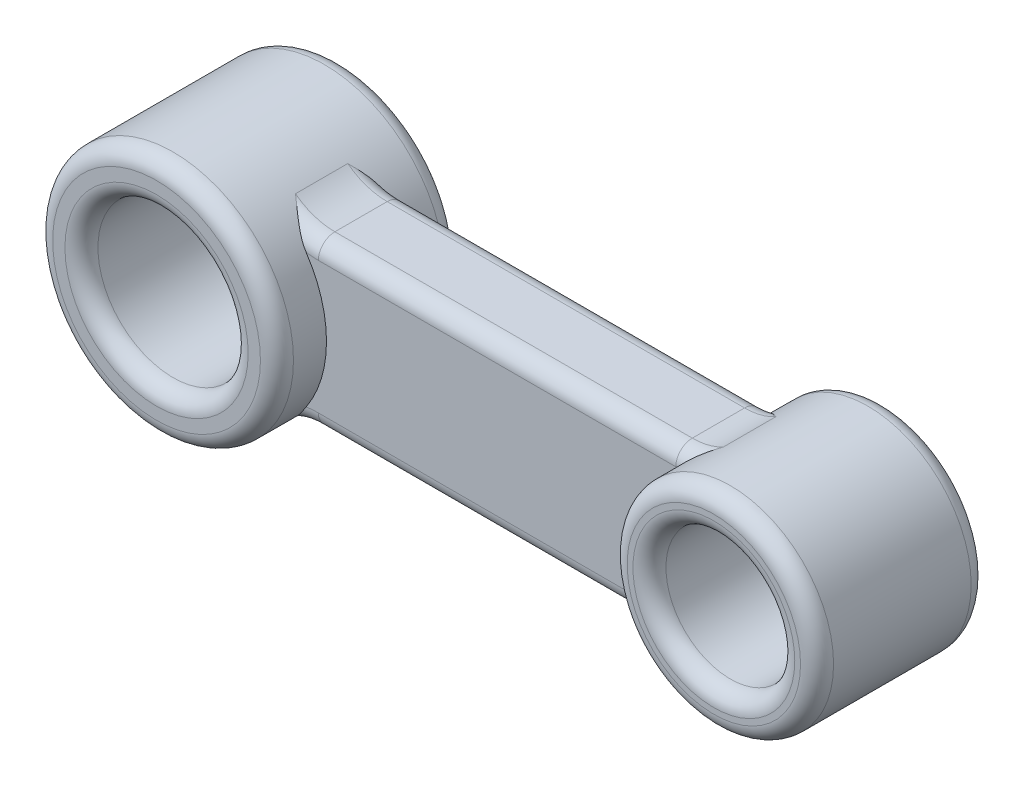
SolidWorks part; units mm, degrees
ref_plane "Front Plane" through (0, 0, 0) normal (0, 0, 1) x (1, 0, 0)
ref_plane "Top Plane" through (0, 0, 0) normal (0, 1, 0) x (1, 0, 0)
ref_plane "Right Plane" through (0, 0, 0) normal (1, 0, 0) x (0, 0, -1)
sketch "Sketch1" plane through (0, 0, 0) normal (0, 0, 1) x (1, 0, 0)
  line L0 (-58.0156, 0) -> (55.3762, 0) construction
  line L2 (-25.5034, 15.24) -> (40.4737, 15.24)
  line L4 (-25.5034, -15.24) -> (40.4737, -15.24)
  circle A0 centre (-46.2238, 0) radius 13.8684
  arc A1 (-32.7684, 17.6891) -> (-32.7684, -17.6891) centre (-46.2238, 0) ccw
  arc A2 (46.2331, -16.7125) -> (46.2331, 16.7125) centre (55.3762, 0) ccw
  circle A3 centre (55.3762, 0) radius 11.8872
  arc A4 (46.2331, -16.7125) -> (40.4737, -15.24) centre (40.4737, -27.24) ccw
  arc A5 (46.2331, 16.7125) -> (40.4737, 15.24) centre (40.4737, 27.24) cw
  arc A6 (-32.7684, -17.6891) -> (-25.5034, -15.24) centre (-25.5034, -27.24) cw
  arc A7 (-25.5034, 15.24) -> (-32.7684, 17.6891) centre (-25.5034, 27.24) cw
  arc A8 (-32.7684, -17.6891) -> (-32.7684, 17.6891) centre (-46.2238, 0) ccw
  arc A9 (46.2331, 16.7125) -> (46.2331, -16.7125) centre (55.3762, 0) ccw
  point P3 (0, 0)
  dimension "D1" = 27.7368
  dimension "D2" = 44.45
  dimension "D3" = 38.1
  dimension "D4" = 23.7744
  dimension "D7" = 12
  dimension "D5" = 101.6
  dimension "D6" = 30.48
extrude "Boss-Extrude1" add sketch "Sketch1" along normal mid plane 34.036 contours A0 A8 A1 region at (-24.6274, 0, 0)
extrude "Boss-Extrude2" add sketch "Sketch1<3>" along normal mid plane 31.496 separate body contours A2 A9 A3 region at (73.8874, 0, 0)
sketch "Sketch1<3>" plane through (0, 0, 0) normal (0, 0, 1) x (1, 0, 0) same geometry as "Sketch1"
extrude "Boss-Extrude3" add sketch "Sketch1<4>" along normal mid plane 15.748 contours A8 L0 A9 A5 L2 A7 | L0 A8 A6 L4 A4 A9 region at (6.3365, 7.9013, 0) region at (6.3365, -7.9013, 0)
sketch "Sketch1<4>" plane through (0, 0, 0) normal (0, 0, 1) x (1, 0, 0) same geometry as "Sketch1"
fillet "Fillet2" radius 3.048 12 edges at (7.4851, -15.24, 7.874) (7.4851, -15.24, -7.874) (7.4851, 15.24, 7.874) (7.4851, 15.24, -7.874) (43.446, -15.6139, 7.874) (43.446, -15.6139, -7.874) (-29.3368, -15.8687, 7.874) (-29.3368, -15.8687, -7.874) (43.446, 15.6139, 7.874) (43.446, 15.6139, -7.874) (-29.3368, 15.8687, 7.874) (-29.3368, 15.8687, -7.874)
fillet "Fillet3" radius 3.048 8 edges at (74.4262, 0, 15.748) (67.2634, 0, 15.748) (74.4262, 0, -15.748) (67.2634, 0, -15.748) (-32.3554, 0, -17.018) (-23.9988, 0, -17.018) (-32.3554, 0, 17.018) (-23.9988, 0, 17.018)
